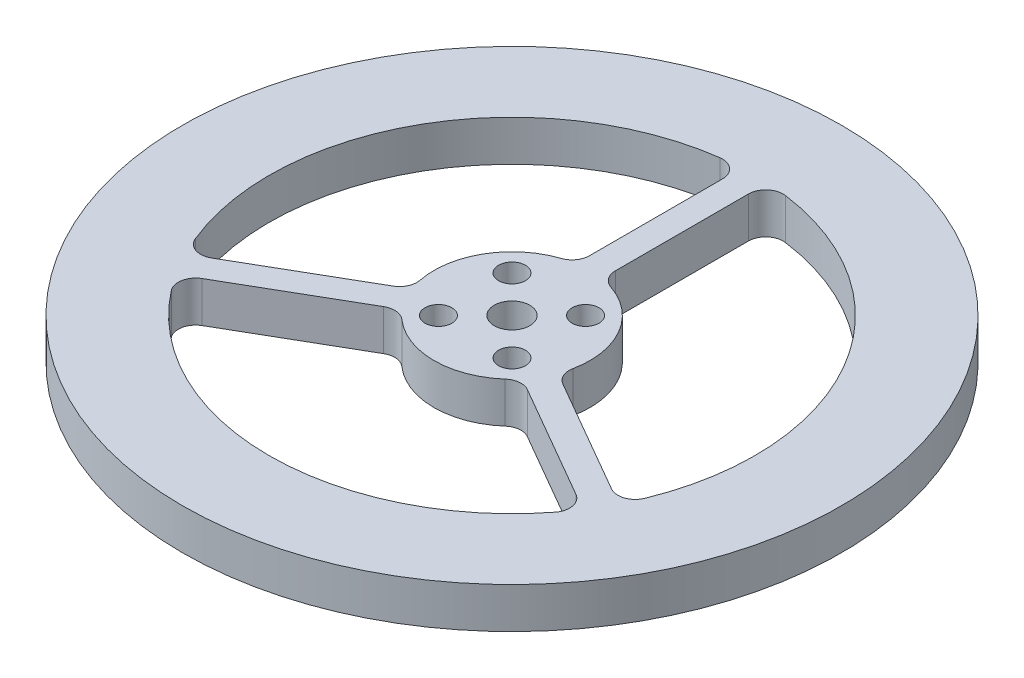
SolidWorks part; units mm, degrees
ref_plane "Front Plane" through (0, 0, 0) normal (0, 0, 1) x (1, 0, 0)
ref_plane "Top Plane" through (0, 0, 0) normal (0, 1, 0) x (1, 0, 0)
ref_plane "Right Plane" through (0, 0, 0) normal (1, 0, 0) x (0, 0, -1)
sketch "Sketch1" plane through (0, 0, 0) normal (0, 1, 0) x (1, 0, 0)
  circle A40 centre (0, 0) radius 38 construction
  circle A41 centre (0, 0) radius 28 construction
  circle A44 centre (0, 0) radius 28
  circle A45 centre (0, 0) radius 38
  dimension "D2" = 76
  dimension "D3" = 56
  dimension "D15" = 76
  dimension "D16" = 56
extrude "Boss-Extrude1" add sketch "Sketch1" along normal blind 4.7
sketch "Sketch2" plane through (0, 0, 0) normal (0, 1, 0) x (1, 0, 0)
  line L6 (-4.2426, 4.2426) -> (4.2426, -4.2426) construction
  line L7 (-4.2426, -4.2426) -> (4.2426, 4.2426) construction
  circle A7 centre (0, 0) radius 2.05
  circle A20 centre (-4.2426, 4.2426) radius 1.55
  circle A21 centre (-4.2426, -4.2426) radius 1.55
  circle A22 centre (4.2426, -4.2426) radius 1.55
  circle A23 centre (4.2426, 4.2426) radius 1.55
  circle A36 centre (-4.2426, -4.2426) radius 2.95 construction
  circle A37 centre (-4.2426, 4.2426) radius 2.95 construction
  circle A38 centre (4.2426, -4.2426) radius 2.95 construction
  circle A39 centre (4.2426, 4.2426) radius 2.95 construction
  circle A42 centre (0, 0) radius 9
  point P44 (0, 0)
  point P45 (0, 0)
  point P55 (0, 0)
  dimension "D2" = 4.1
  dimension "D3" = 18
  dimension "D4" = 3.1
  dimension "D5" = 12
  dimension "D13" = 5.9
extrude "Boss-Extrude2" add sketch "Sketch2" along normal up to surface (4.7 mm away) separate body up to face at (0, 4.7, 38)
sketch "Sketch3" plane through (0, 0, 0) normal (0, 1, 0) x (1, 0, 0)
  line L0 (0, 0) -> (0, 33) construction
  line L1 (-1.5, 29) -> (-1.5, 8.8741)
  line L2 (1.5, 29) -> (1.5, 8.8741)
  line L3 (-1.5, 15) -> (1.5, 15) construction
  line L4 (-1.5, 8.8741) -> (1.5, 8.8741)
  line L5 (-1.5, 29) -> (1.5, 29)
  line L6 (25.8647, -13.201) -> (24.3647, -15.799)
  line L7 (24.3647, -15.799) -> (6.9352, -5.7361)
  line L8 (8.4352, -3.138) -> (6.9352, -5.7361)
  line L9 (25.8647, -13.201) -> (8.4352, -3.138)
  line L10 (13.7404, -6.201) -> (12.2404, -8.799) construction
  line L11 (-24.3647, -15.799) -> (-25.8647, -13.201)
  line L12 (-25.8647, -13.201) -> (-8.4352, -3.138)
  line L13 (-6.9352, -5.7361) -> (-8.4352, -3.138)
  line L14 (-24.3647, -15.799) -> (-6.9352, -5.7361)
  line L15 (-12.2404, -8.799) -> (-13.7404, -6.201) construction
  circle A0 centre (0, 0) radius 9 construction
  point P9 (0, 15)
  point P25 (0, 0)
  dimension "D1" = 3
  dimension "D2" = 3
extrude "Boss-Extrude3" add sketch "Sketch3" along normal up to surface (4.7 mm away) up to face at (0, 4.7, 38)
fillet "Fillet1" radius 2 6 edges at (24.9639, 2.35, 12.6809) (23.4639, 2.35, 15.2789) (1.5, 2.35, -27.9598) (-1.5, 2.35, -27.9598) (-24.9639, 2.35, 12.6809) (-23.4639, 2.35, 15.2789)
fillet "Fillet2" radius 2 6 edges at (1.5, 2.35, -8.8741) (-1.5, 2.35, -8.8741) (-8.4352, 2.35, 3.138) (8.4352, 2.35, 3.138) (6.9352, 2.35, 5.7361) (-6.9352, 2.35, 5.7361)
